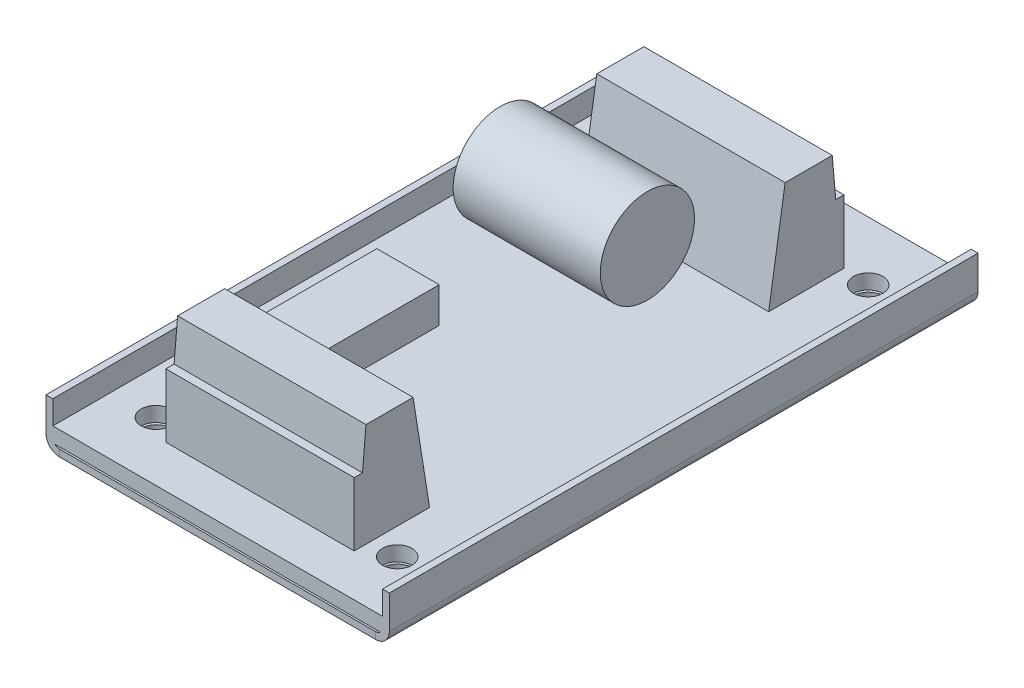
SolidWorks part; units mm, degrees
note: The reader was unsure of these and kept them because the rebuilt part matched: flange length of "Edge-Flange1".
ref_plane "Front Plane" through (0, 0, 0) normal (0, 0, 1) x (1, 0, 0)
ref_plane "Top Plane" through (0, 0, 0) normal (0, 1, 0) x (1, 0, 0)
ref_plane "Right Plane" through (0, 0, 0) normal (1, 0, 0) x (0, 0, -1)
sketch "Sketch1" plane through (0, 0, 0) normal (0, 1, 0) x (1, 0, 0)
  line L1 (-17.78, -31.75) -> (17.78, -31.75)
  line L2 (-17.78, -31.75) -> (-17.78, 31.75)
  line L3 (-17.78, 31.75) -> (17.78, 31.75)
  line L4 (17.78, -31.75) -> (17.78, 31.75)
  line L5 (-17.78, -31.75) -> (17.78, 31.75) construction
  line L6 (-17.78, 31.75) -> (17.78, -31.75) construction
  point P0 (0, 0)
  dimension "D1" = 63.5
  dimension "D2" = 35.56
base flange "Base-Flange1" sketch "Sketch1" thickness 0.7366 reverse thickness direction no parameters "D1"=0.7366
edge flange "Edge-Flange1" sketch "Sketch10" flange profiles "Sketch10", "Sketch11" flange angle 90 flange length 5.08 flange position material outside bend radius 0.7366 thickness 0.7366 parameters "D6"=10, "D8"=0.254
sketch "Sketch10" plane through (-17.78, 0, 0) normal (-1, 0, 0) x (0, 0, 1)
  line L2 (-31.75, 0) -> (-31.75, 4.3434)
  line L3 (-31.75, 4.3434) -> (31.75, 4.3434)
  line L4 (31.75, 4.3434) -> (31.75, 0)
  line L5 (-31.75, 0) -> (31.75, 0) construction
  line L6 (-31.75, 0) -> (31.75, 0)
sketch "Sketch11" plane through (17.78, 0, 0) normal (1, 0, 0) x (0, 0, -1)
  line L0 (-31.75, 0) -> (31.75, 0) construction
  line L1 (-31.75, 0) -> (31.75, 0)
  line L2 (-31.75, 0) -> (-31.75, 4.3434)
  line L3 (-31.75, 4.3434) -> (31.75, 4.3434)
  line L4 (31.75, 4.3434) -> (31.75, 0)
bend "EdgeBend1" bend radius 0.7366 bend angle 90 parameters "D5"=1
bend "EdgeBend2" bend radius 0.7366 bend angle 90 parameters "D5"=2
sketch "Sketch12" plane through (0, 0, 31.75) normal (0, 0, 1) x (1, 0, 0)
  line L0 (-17.78, 0.7366) -> (-17.78, 4.3434) construction
  line L1 (-17.78, 1.8034) -> (17.78, 1.8034)
  line L2 (-17.78, 1.8034) -> (-17.78, 0.2032)
  line L3 (-17.78, 0.2032) -> (17.78, 0.2032)
  line L4 (17.78, 1.8034) -> (17.78, 0.2032)
  line L5 (17.78, 4.3434) -> (17.78, 0.7366) construction
  line L6 (-17.0434, -0.7366) -> (17.0434, -0.7366) construction
  dimension "D1" = 1.6002
  dimension "D2" = 2.54
extrude "Boss-Extrude1" add sketch "Sketch12" against normal through all
sketch "Sketch13" plane through (0, -0.7366, 0) normal (0, -1, 0) x (1, 0, 0)
  line L1 (13.0175, -25.4) -> (-13.0175, -25.4) construction
  line L2 (13.0175, -25.4) -> (13.0175, 25.4) construction
  line L3 (13.0175, 25.4) -> (-13.0175, 25.4) construction
  line L4 (-13.0175, -25.4) -> (-13.0175, 25.4) construction
  line L5 (13.0175, -25.4) -> (-13.0175, 25.4) construction
  line L6 (13.0175, 25.4) -> (-13.0175, -25.4) construction
  circle A0 centre (-13.0175, 25.4) radius 1.5875
  circle A1 centre (13.0175, 25.4) radius 1.5875
  circle A2 centre (13.0175, -25.4) radius 1.5875
  circle A3 centre (-13.0175, -25.4) radius 1.5875
  point P8 (0, 0)
  dimension "D1" = 3.175
  dimension "D2" = 26.035
  dimension "D3" = 50.8
extrude "Cut-Extrude1" cut sketch "Sketch13" against normal through all
sketch "Sketch14" plane through (0, 0, 0) normal (1, 0, 0) x (0, 0, -1)
  line L0 (17.526, 1.8034) -> (25.654, 1.8034)
  line L1 (25.654, 1.8034) -> (25.654, 8.6614)
  line L2 (25.654, 8.6614) -> (24.765, 8.6614)
  line L3 (24.765, 8.6614) -> (24.384, 12.9794)
  line L4 (24.384, 12.9794) -> (19.304, 12.9794)
  line L5 (19.304, 12.9794) -> (17.526, 1.8034)
  line L6 (31.75, 1.8034) -> (-31.75, 1.8034) construction
  line L7 (-0.762, 4.3434) -> (-0.762, -0.7366) construction
  line L8 (-20.828, 12.9794) -> (-19.05, 1.8034)
  line L9 (-25.908, 12.9794) -> (-20.828, 12.9794)
  line L10 (-26.289, 8.6614) -> (-25.908, 12.9794)
  line L11 (-27.178, 8.6614) -> (-26.289, 8.6614)
  line L12 (-27.178, 1.8034) -> (-27.178, 8.6614)
  line L13 (-19.05, 1.8034) -> (-27.178, 1.8034)
  line L14 (31.75, -0.7366) -> (-31.75, -0.7366) construction
  line L15 (-31.75, 4.3434) -> (31.75, 4.3434) construction
  dimension "D1" = 8.128
  dimension "D2" = 0.889
  dimension "D3" = 5.08
  dimension "D4" = 6.096
  dimension "D5" = 13.716
  dimension "D6" = 9.398
  dimension "D7" = 1.27
  dimension "D8" = 4.572
extrude "Boss-Extrude2" add sketch "Sketch14" along normal mid plane 20.32
sketch "Sketch15" plane through (0, 0, 0) normal (1, 0, 0) x (0, 0, -1)
  line L0 (31.75, 1.8034) -> (-31.75, 1.8034) construction
  circle A0 centre (12.065, 6.8834) radius 5.08
  point P2 (12.065, 1.8034)
  dimension "D1" = 10.16
  dimension "D2" = 19.685
extrude "Boss-Extrude3" add sketch "Sketch15" against normal blind 15.875 from offset 2.54 separate body
sketch "Sketch16" plane through (0, 1.8034, 0) normal (0, 1, 0) x (1, 0, 0)
  line L0 (17.78, -31.75) -> (-17.78, -31.75) construction
  line L1 (-6.3246, -18.161) -> (-13.0556, -18.161)
  line L2 (-6.3246, -18.161) -> (-6.3246, -1.524)
  line L3 (-6.3246, -1.524) -> (-13.0556, -1.524)
  line L4 (-13.0556, -18.161) -> (-13.0556, -1.524)
  line L5 (-18.5166, -31.75) -> (-18.5166, 31.75) construction
  dimension "D1" = 30.226
  dimension "D2" = 16.637
  dimension "D3" = 6.731
  dimension "D4" = 12.192
extrude "Boss-Extrude4" add sketch "Sketch16" along normal blind 3.81
sketch "Bend-Lines1" [suppressed] plane through (0, 0, 0) normal (0, 1, 0) x (1, 0, 0)
sketch "Bounding-Box1" [suppressed] plane through (0, 0, 0) normal (0, 1, 0) x (1, 0, 0)
sheet metal parameters "Sheet-Metal1" thickness 0.7366 parameters "D1"=0.7366
flat pattern "Flat-Pattern1" [suppressed]
sketch "Bend-Lines2" plane through (0, 0, 0) normal (0, 1, 0) x (1, 0, 0)
sketch "Bounding-Box2" [suppressed] plane through (0, 0, 0) normal (0, 1, 0) x (1, 0, 0)
sheet metal parameters "Sheet-Metal2" thickness 0.7366 parameters "D1"=0.7366
flat pattern "Flat-Pattern1"
sketch "Bend-Lines2" plane through (0, 0, 0) normal (0, 1, 0) x (1, 0, 0)
  line L0 (17.9112, -31.75) -> (17.9112, 31.75) construction
  line L1 (-17.9112, 31.75) -> (-17.9112, -31.75) construction
  line L2 (17.9112, -31.75) -> (17.9112, 31.75) construction
  line L3 (-17.9112, 31.75) -> (-17.9112, -31.75) construction
sketch3d "Bounding-Box2" [suppressed]
  line L0 (-22.3858, -31.75, 0) -> (-22.3858, 31.75, 0) construction
  line L1 (22.3858, -31.75, 0) -> (22.3858, 31.75, 0) construction
  line L2 (-22.3858, -31.75, 0) -> (22.3858, -31.75, 0) construction
  line L3 (-22.3858, 31.75, 0) -> (22.3858, 31.75, 0) construction
bend of the flat pattern "Flatten-<EdgeBend1>1"
bend of the flat pattern "Flatten-<EdgeBend2>1"
sheet metal parameters "Sheet-Metal3" thickness 0.7366 parameters "D1"=0.7366
flat pattern "Flat-Pattern1"
sketch "Bend-Lines2" plane through (0, 0, 0) normal (0, 1, 0) x (1, 0, 0)
  line L0 (17.9112, -31.75) -> (17.9112, 31.75) construction
  line L1 (-17.9112, 31.75) -> (-17.9112, -31.75) construction
  line L2 (17.9112, -31.75) -> (17.9112, 31.75) construction
  line L3 (-17.9112, 31.75) -> (-17.9112, -31.75) construction
sketch3d "Bounding-Box2" [suppressed]
  line L0 (-22.3858, -31.75, 0) -> (-22.3858, 31.75, 0) construction
  line L1 (22.3858, -31.75, 0) -> (22.3858, 31.75, 0) construction
  line L2 (-22.3858, -31.75, 0) -> (22.3858, -31.75, 0) construction
  line L3 (-22.3858, 31.75, 0) -> (22.3858, 31.75, 0) construction
bend of the flat pattern "Flatten-<EdgeBend1>1"
bend of the flat pattern "Flatten-<EdgeBend2>1"
sheet metal parameters "Sheet-Metal4" thickness 0.7366 parameters "D1"=0.7366
flat pattern "Flat-Pattern1"
sketch "Bend-Lines2" plane through (0, 0, 0) normal (0, 1, 0) x (1, 0, 0)
  line L0 (17.9112, -31.75) -> (17.9112, 31.75) construction
  line L1 (-17.9112, 31.75) -> (-17.9112, -31.75) construction
  line L2 (17.9112, -31.75) -> (17.9112, 31.75) construction
  line L3 (-17.9112, 31.75) -> (-17.9112, -31.75) construction
sketch3d "Bounding-Box2" [suppressed]
  line L0 (-22.3858, -31.75, 0) -> (-22.3858, 31.75, 0) construction
  line L1 (22.3858, -31.75, 0) -> (22.3858, 31.75, 0) construction
  line L2 (-22.3858, -31.75, 0) -> (22.3858, -31.75, 0) construction
  line L3 (-22.3858, 31.75, 0) -> (22.3858, 31.75, 0) construction
bend of the flat pattern "Flatten-<EdgeBend1>1"
bend of the flat pattern "Flatten-<EdgeBend2>1"
sheet metal parameters "Sheet-Metal5" thickness 0.7366 parameters "D1"=0.7366
flat pattern "Flat-Pattern1"
sketch "Bend-Lines2" plane through (0, 0, 0) normal (0, 1, 0) x (1, 0, 0)
  line L0 (17.9112, -31.75) -> (17.9112, 31.75) construction
  line L1 (-17.9112, 31.75) -> (-17.9112, -31.75) construction
  line L2 (17.9112, -31.75) -> (17.9112, 31.75) construction
  line L3 (-17.9112, 31.75) -> (-17.9112, -31.75) construction
sketch3d "Bounding-Box2" [suppressed]
  line L0 (-22.3858, -31.75, 0) -> (-22.3858, 31.75, 0) construction
  line L1 (22.3858, -31.75, 0) -> (22.3858, 31.75, 0) construction
  line L2 (-22.3858, -31.75, 0) -> (22.3858, -31.75, 0) construction
  line L3 (-22.3858, 31.75, 0) -> (22.3858, 31.75, 0) construction
bend of the flat pattern "Flatten-<EdgeBend1>1"
bend of the flat pattern "Flatten-<EdgeBend2>1"
sheet metal parameters "Sheet-Metal7" thickness 0.7366 parameters "D1"=0.7366
flat pattern "Flat-Pattern1"
sketch "Bend-Lines2" plane through (0, 0, 0) normal (0, 1, 0) x (1, 0, 0)
  line L0 (17.9112, -31.75) -> (17.9112, 31.75) construction
  line L1 (-17.9112, 31.75) -> (-17.9112, -31.75) construction
  line L2 (17.9112, -31.75) -> (17.9112, 31.75) construction
  line L3 (-17.9112, 31.75) -> (-17.9112, -31.75) construction
sketch3d "Bounding-Box2" [suppressed]
  line L0 (-22.3858, -31.75, 0) -> (-22.3858, 31.75, 0) construction
  line L1 (22.3858, -31.75, 0) -> (22.3858, 31.75, 0) construction
  line L2 (-22.3858, -31.75, 0) -> (22.3858, -31.75, 0) construction
  line L3 (-22.3858, 31.75, 0) -> (22.3858, 31.75, 0) construction
bend of the flat pattern "Flatten-<EdgeBend1>1"
bend of the flat pattern "Flatten-<EdgeBend2>1"
